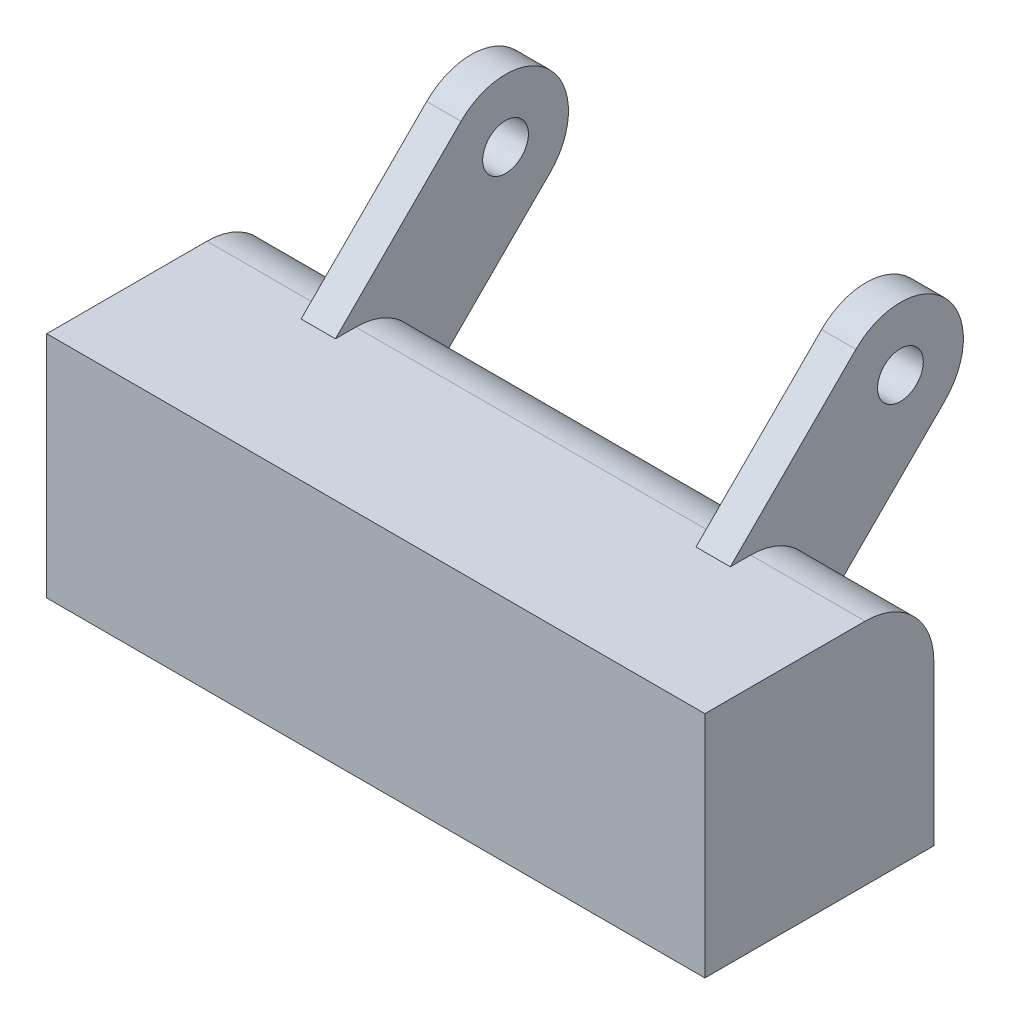
SolidWorks part; units mm, degrees
ref_plane "Спереди" through (0, 0, 0) normal (0, 0, 1) x (1, 0, 0)
ref_plane "Сверху" through (0, 0, 0) normal (0, 1, 0) x (1, 0, 0)
ref_plane "Справа" through (0, 0, 0) normal (1, 0, 0) x (0, 0, -1)
sketch "Sketch1" plane through (0, 0, 0) normal (1, 0, 0) x (0, 0, -1)
  line L1 (-6, 0) -> (-20, 0)
  line L2 (0, -6) -> (0, -20)
  line L3 (0, -20) -> (-20, -20)
  line L4 (-20, 0) -> (-20, -20)
  arc A0 (0, -6) -> (-6, 0) centre (-6, -6) ccw
  point P7 (0, 0)
  dimension "D1" = 6
extrude "Extrude1" add sketch "Sketch1" along normal mid plane 57.5
sketch "Sketch2" plane through (0, 0, 0) normal (1, 0, 0) x (0, 0, -1)
  line L0 (-6, -6) -> (-1.7574, -1.7574)
  line L1 (-1.7574, -1.7574) -> (10.9706, 10.9706)
  line L2 (7.0815, 7.0815) -> (10.9706, 3.1924)
  line L3 (10.9706, 3.1924) -> (-6.7071, -14.4853)
  line L4 (7.0815, 7.0815) -> (3.1924, 10.9706)
  line L5 (3.1924, 10.9706) -> (-14.4853, -6.7071)
  line L6 (-14.4853, -6.7071) -> (-6.7071, -14.4853)
  circle A1 centre (7.0815, 7.0815) radius 5.5
  circle A3 centre (7.0815, 7.0815) radius 2
  dimension "D1" = 5.5
  dimension "D3" = 4
  dimension "D2" = 18
  dimension "D4" = 11
extrude "Extrude2" add sketch "Sketch2" against normal blind 3 from offset 18.75 contours A1 L5 L6 L3 | A3 L1 A1 L2 | A3 L1 A1 L4 | A3 L2 A1 L1 | A3 L4 A1 L1 region at (0, 7.0815, -3.4602) region at (0, 1.2215, -7.0815) region at (0, 3.4602, -7.0815) region at (0, 10.7027, -7.0815) region at (0, 7.0815, -10.7027)
extrude "Extrude3" add sketch "Sketch" along normal blind 3 from offset 18.75 contours A1 L5 L6 L3 | A3 L1 A1 L2 | A3 L2 A1 L1 | A3 L1 A1 L4 | A3 L4 A1 L1 region at (0, 7.0815, -3.4602) region at (0, 1.2215, -7.0815) region at (0, 3.4602, -7.0815) region at (0, 10.7027, -7.0815) region at (0, 7.0815, -10.7027) offset against normal yes
sketch "Sketch" plane through (0, 0, 0) normal (1, 0, 0) x (0, 0, -1) same geometry as "Sketch2"
